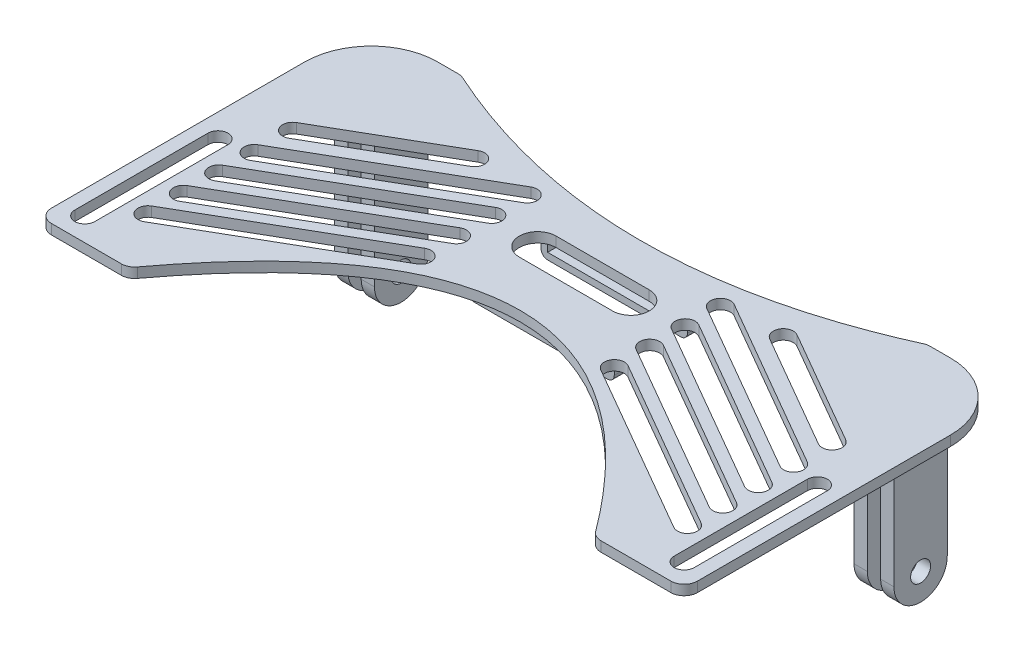
SolidWorks part; units mm, degrees
ref_plane "前视基准面" through (0, 0, 0) normal (0, 0, 1) x (1, 0, 0)
ref_plane "上视基准面" through (0, 0, 0) normal (0, 1, 0) x (1, 0, 0)
ref_plane "右视基准面" through (0, 0, 0) normal (1, 0, 0) x (0, 0, -1)
sketch "草图2" plane through (0, 0, 0) normal (0, 1, 0) x (1, 0, 0)
  line L0 (-39, 0) -> (39, 0) construction
  line L2 (-43, -6) -> (-35, -6)
  line L3 (-43, -6) -> (-43, 6)
  line L4 (-43, 6) -> (-35, 6)
  line L5 (-35, -6) -> (-35, 6)
  line L6 (-43, -6) -> (-35, 6) construction
  line L7 (-43, 6) -> (-35, -6) construction
  line L8 (35, -6) -> (43, -6)
  line L9 (35, -6) -> (35, 6)
  line L10 (35, 6) -> (43, 6)
  line L11 (43, -6) -> (43, 6)
  line L12 (35, -6) -> (43, 6) construction
  line L13 (35, 6) -> (43, -6) construction
  point P2 (0, 0)
  dimension "D1" = 78
  dimension "D2" = 8
  dimension "D3" = 8
  dimension "D4" = 12
extrude "凸台-拉伸1" add sketch "草图2" along normal blind 1.5
sketch "草图3" plane through (0, 0, 0) normal (0, 1, 0) x (1, 0, 0)
  line L0 (-39, 0) -> (39, 0) construction
  line L1 (-38, 4) -> (-36, 4)
  line L2 (-38, 4) -> (-38, -4)
  line L3 (-38, -4) -> (-36, -4)
  line L4 (-36, 4) -> (-36, -4)
  line L5 (-38, 4) -> (-36, -4) construction
  line L6 (-38, -4) -> (-36, 4) construction
  line L7 (-39, -6) -> (-39, 6) construction
  line L8 (-43, -6) -> (-35, -6) construction
  line L9 (-43, 6) -> (-35, 6) construction
  line L10 (-40, -4) -> (-42, 4) construction
  line L11 (-40, 4) -> (-42, -4) construction
  line L12 (-42, 4) -> (-42, -4)
  line L13 (-40, -4) -> (-42, -4)
  line L14 (-40, 4) -> (-40, -4)
  line L15 (-40, 4) -> (-42, 4)
  line L16 (0, -18.8459) -> (0, 19.8172) construction
  line L17 (40, 4) -> (42, -4) construction
  line L18 (40, -4) -> (42, 4) construction
  line L19 (39, -6) -> (39, 6) construction
  line L20 (38, -4) -> (36, 4) construction
  line L21 (38, 4) -> (36, -4) construction
  line L22 (40, 4) -> (42, 4)
  line L23 (40, 4) -> (40, -4)
  line L24 (40, -4) -> (42, -4)
  line L25 (42, 4) -> (42, -4)
  line L26 (36, 4) -> (36, -4)
  line L27 (38, -4) -> (36, -4)
  line L28 (38, 4) -> (38, -4)
  line L29 (38, 4) -> (36, 4)
  point P0 (-37, 0)
  point P18 (-41, 0)
  point P32 (41, 0)
  point P33 (37, 0)
  dimension "D1" = 1
  dimension "D2" = 2
  dimension "D3" = 8
extrude "凸台-拉伸2" add sketch "草图3" against normal blind 24.5
fillet "圆角1" radius 4 4 edges at (-41, -24.5, -4) (-37, -24.5, -4) (-37, -24.5, 4) (-41, -24.5, 4)
fillet "圆角2" radius 4 4 edges at (37, -24.5, 4) (41, -24.5, 4) (41, -24.5, -4) (37, -24.5, -4)
sketch "草图4" plane through (43, 0, 0) normal (1, 0, 0) x (0, 0, -1)
  circle A0 centre (0, -20.5) radius 1.5
  circle A1 centre (0, -20.5) radius 4 construction
  dimension "D1" = 3
extrude "切除-拉伸1" cut sketch "草图4" against normal through all
sketch "草图6" plane through (0, 0, 0) normal (0, 1, 0) x (1, 0, 0)
  line L0 (45, -18.5) -> (45, -38.5) construction
  line L1 (38.5, 8) -> (-38.5, 8) construction
  line L2 (48.5, -2) -> (48.5, -40)
  line L3 (-45, -18.5) -> (-45, -38.5) construction
  line L4 (-43.5, -18.5) -> (-43.5, -38.5)
  line L5 (-46.5, -18.5) -> (-46.5, -38.5)
  line L6 (45, 0) -> (-45, 0) construction
  line L7 (46.5, -42) -> (35, -42)
  line L8 (-48.5, -2) -> (-48.5, -40)
  line L9 (46.5, -18.5) -> (46.5, -38.5)
  line L10 (43.5, -18.5) -> (43.5, -38.5)
  line L11 (-35, 6) -> (-43, 6) construction
  line L13 (-38.5, 8) -> (-35, 8)
  line L14 (35, 8) -> (38.5, 8)
  line L15 (0, 0) -> (0, -36.2232) construction
  line L16 (-35, -42) -> (-46.5, -42)
  arc A0 (-43.5, -18.5) -> (-46.5, -18.5) centre (-45, -18.5) ccw
  arc A1 (-46.5, -38.5) -> (-43.5, -38.5) centre (-45, -38.5) ccw
  arc A2 (46.5, -18.5) -> (43.5, -18.5) centre (45, -18.5) ccw
  arc A3 (43.5, -38.5) -> (46.5, -38.5) centre (45, -38.5) ccw
  arc A4 (48.5, -2) -> (38.5, 8) centre (38.5, -2) ccw
  arc A5 (-38.5, 8) -> (-48.5, -2) centre (-38.5, -2) ccw
  arc A6 (-46.5, -42) -> (-48.5, -40) centre (-46.5, -40) cw
  arc A7 (48.5, -40) -> (46.5, -42) centre (46.5, -40) cw
  spline S0 degree 2 poles (-35, 8) (0, -8) (35, 8) knots 0 0 0 1 1 1
  spline S1 degree 2 poles (-35, -42) (0, 5.7768) (35, -42) knots 0 0 0 1 1 1
  point P0 (0, 0)
  point P5 (0, 0)
  point P8 (-45, -28.5)
  point P15 (45, -28.5)
  point P29 (-35, 8)
  point P30 (35, 8)
  point P43 (-35, -42)
  point P45 (35, -42)
  point P50 (0, -18.1116)
  dimension "D8" = 10
  dimension "D9" = 2
  dimension "D10" = 2
  dimension "D1" = 2
  dimension "D2" = 3
  dimension "D3" = 90
  dimension "D4" = 3
  dimension "D5" = 2
  dimension "D6" = 2
  dimension "D7" = 3.5
  dimension "D11" = 20
  dimension "D13" = 50
extrude "凸台-拉伸3" add sketch "草图6" along normal blind 1.5 contours L16 S1 L7 A7 L2 A4 L14 S0 L13 A5 L8 A6 A1 L5 A0 L4 A3 L10 A2 L9 region at (0, 0, 13.9569)
sketch "草图8" plane through (0, 0, 0) normal (0, -1, 0) x (-1, 0, 0)
  line L1 (11, -2) -> (-11, -2)
  line L2 (11, -2) -> (11, -4)
  line L3 (11, -4) -> (-11, -4)
  line L4 (-11, -2) -> (-11, -4)
  line L5 (11, -2) -> (-11, -4) construction
  line L6 (11, -4) -> (-11, -2) construction
  line L7 (11, -13) -> (-11, -13)
  line L8 (11, -13) -> (11, -15)
  line L9 (11, -15) -> (-11, -15)
  line L10 (-11, -13) -> (-11, -15)
  line L11 (11, -13) -> (-11, -15) construction
  line L12 (11, -15) -> (-11, -13) construction
  point P0 (0, -3)
  point P5 (0, -14)
  dimension "D1" = 22
  dimension "D2" = 2
  dimension "D3" = 2
  dimension "D4" = 22
  dimension "D5" = 2
  dimension "D6" = 9
extrude "凸台-拉伸4" add sketch "草图8" along normal blind 4
sketch "草图9" plane through (0, 0, 15) normal (0, 0, 1) x (1, 0, 0)
  line L0 (-11, -4) -> (-11, 0) construction
  line L1 (11, -4) -> (-11, -4) construction
  line L2 (11, -4) -> (11, 0) construction
  line L3 (11, 0) -> (-11, 0) construction
  line L4 (-11, -4) -> (-11, 0) construction
  line L5 (11, -4) -> (-11, -4) construction
  line L6 (11, -4) -> (11, 0) construction
  line L7 (11, 0) -> (-11, 0) construction
  line L8 (-10, -3) -> (-10, 0)
  line L9 (-10, 0) -> (10, 0)
  line L10 (10, 0) -> (10, -3)
  line L11 (10, -3) -> (-10, -3)
  line L12 (10, -1) -> (-10, -1) construction
  line L13 (-10, -3) -> (-10, -1) construction
  line L14 (10, -3) -> (10, -1) construction
  dimension "D1" = 1
extrude "切除-拉伸2" cut sketch "草图9" against normal through all
fillet "圆角4" radius 2 4 edges at (-35, 0.75, -8) (35, 0.75, -8) (35, 0.75, 42) (-35, 0.75, 42)
sketch "草图13" plane through (0, 1.5, 0) normal (0, 1, 0) x (1, 0, 0)
  line L0 (-40.5, -33.5) -> (-14.5192, -18.5) construction
  line L1 (-41.25, -32.201) -> (-15.2692, -17.201)
  line L2 (-39.75, -34.799) -> (-13.7692, -19.799)
  line L3 (-36.009, -42) -> (-46.5, -42) construction
  line L4 (-48.5, -2) -> (-48.5, -40) construction
  line L5 (-40.5, -28.1884) -> (-14.5192, -13.1884) construction
  line L6 (-41.25, -26.8893) -> (-15.2692, -11.8893)
  line L7 (-39.75, -29.4874) -> (-13.7692, -14.4874)
  line L8 (-40.5, -22.8768) -> (-14.5192, -7.8768) construction
  line L9 (-41.25, -21.5777) -> (-15.2692, -6.5777)
  line L10 (-39.75, -24.1758) -> (-13.7692, -9.1758)
  line L11 (-40.5, -17.5651) -> (-14.5192, -2.5651) construction
  line L12 (-41.25, -16.2661) -> (-15.2692, -1.2661)
  line L13 (-39.75, -18.8642) -> (-13.7692, -3.8642)
  line L14 (-40.5, -11.7916) -> (-23.1795, -1.7916) construction
  line L15 (-41.25, -10.4926) -> (-23.9295, -0.4926)
  line L16 (-39.75, -13.0907) -> (-22.4295, -3.0907)
  line L17 (0, -4) -> (0, -13) construction
  line L18 (10, -4) -> (-10, -4) construction
  line L19 (-10, -13) -> (10, -13) construction
  line L20 (-7, -8.5) -> (7, -8.5) construction
  line L21 (-7, -5.75) -> (7, -5.75)
  line L22 (-7, -11.25) -> (7, -11.25)
  line L23 (40.5, -33.5) -> (14.5192, -18.5) construction
  line L24 (41.25, -32.201) -> (15.2692, -17.201)
  line L25 (39.75, -34.799) -> (13.7692, -19.799)
  line L26 (40.5, -28.1884) -> (14.5192, -13.1884) construction
  line L27 (41.25, -26.8893) -> (15.2692, -11.8893)
  line L28 (39.75, -29.4874) -> (13.7692, -14.4874)
  line L29 (40.5, -22.8768) -> (14.5192, -7.8768) construction
  line L30 (41.25, -21.5777) -> (15.2692, -6.5777)
  line L31 (39.75, -24.1758) -> (13.7692, -9.1758)
  line L32 (40.5, -17.5651) -> (14.5192, -2.5651) construction
  line L33 (41.25, -16.2661) -> (15.2692, -1.2661)
  line L34 (39.75, -18.8642) -> (13.7692, -3.8642)
  line L35 (40.5, -11.7916) -> (23.1795, -1.7916) construction
  line L36 (41.25, -10.4926) -> (23.9295, -0.4926)
  line L37 (39.75, -13.0907) -> (22.4295, -3.0907)
  arc A0 (-41.25, -32.201) -> (-39.75, -34.799) centre (-40.5, -33.5) ccw
  arc A1 (-13.7692, -19.799) -> (-15.2692, -17.201) centre (-14.5192, -18.5) ccw
  arc A2 (-41.25, -26.8893) -> (-39.75, -29.4874) centre (-40.5, -28.1884) ccw
  arc A3 (-13.7692, -14.4874) -> (-15.2692, -11.8893) centre (-14.5192, -13.1884) ccw
  arc A4 (-41.25, -21.5777) -> (-39.75, -24.1758) centre (-40.5, -22.8768) ccw
  arc A5 (-13.7692, -9.1758) -> (-15.2692, -6.5777) centre (-14.5192, -7.8768) ccw
  arc A6 (-41.25, -16.2661) -> (-39.75, -18.8642) centre (-40.5, -17.5651) ccw
  arc A7 (-13.7692, -3.8642) -> (-15.2692, -1.2661) centre (-14.5192, -2.5651) ccw
  arc A8 (-41.25, -10.4926) -> (-39.75, -13.0907) centre (-40.5, -11.7916) ccw
  arc A9 (-22.4295, -3.0907) -> (-23.9295, -0.4926) centre (-23.1795, -1.7916) ccw
  arc A10 (-7, -5.75) -> (-7, -11.25) centre (-7, -8.5) ccw
  arc A11 (7, -11.25) -> (7, -5.75) centre (7, -8.5) ccw
  arc A12 (41.25, -32.201) -> (39.75, -34.799) centre (40.5, -33.5) cw
  arc A13 (13.7692, -19.799) -> (15.2692, -17.201) centre (14.5192, -18.5) cw
  arc A14 (41.25, -26.8893) -> (39.75, -29.4874) centre (40.5, -28.1884) cw
  arc A15 (13.7692, -14.4874) -> (15.2692, -11.8893) centre (14.5192, -13.1884) cw
  arc A16 (41.25, -21.5777) -> (39.75, -24.1758) centre (40.5, -22.8768) cw
  arc A17 (13.7692, -9.1758) -> (15.2692, -6.5777) centre (14.5192, -7.8768) cw
  arc A18 (41.25, -16.2661) -> (39.75, -18.8642) centre (40.5, -17.5651) cw
  arc A19 (13.7692, -3.8642) -> (15.2692, -1.2661) centre (14.5192, -2.5651) cw
  arc A20 (41.25, -10.4926) -> (39.75, -13.0907) centre (40.5, -11.7916) cw
  arc A21 (22.4295, -3.0907) -> (23.9295, -0.4926) centre (23.1795, -1.7916) cw
  point P2 (-27.5096, -26)
  point P15 (-27.5096, -20.6884)
  point P22 (-27.5096, -15.3768)
  point P29 (-27.5096, -10.0651)
  point P34 (-31.8397, -6.7916)
  point P47 (0, -8.5)
  point P54 (27.5096, -26)
  point P61 (27.5096, -20.6884)
  point P68 (27.5096, -15.3768)
  point P75 (27.5096, -10.0651)
  point P82 (31.8397, -6.7916)
  dimension "D1" = 3
  dimension "D2" = 30
  dimension "D3" = 30
  dimension "D4" = 8
  dimension "D5" = 16
  dimension "D7" = 3
  dimension "D8" = 2
  dimension "D9" = 1.6
  dimension "D10" = 20
  dimension "D11" = 5.5
  dimension "D12" = 14
  dimension "D6" = 4
extrude "切除-拉伸4" cut sketch "草图13" against normal blind 4
fillet "圆角5" radius 1 4 edges at (36, 0, 0) (-36, 0, 0) (-42, 0, 0) (42, 0, 0)
fillet "圆角6" radius 1 4 edges at (11, -4, 14) (11, -4, 3) (-11, -4, 3) (-11, -4, 14)
